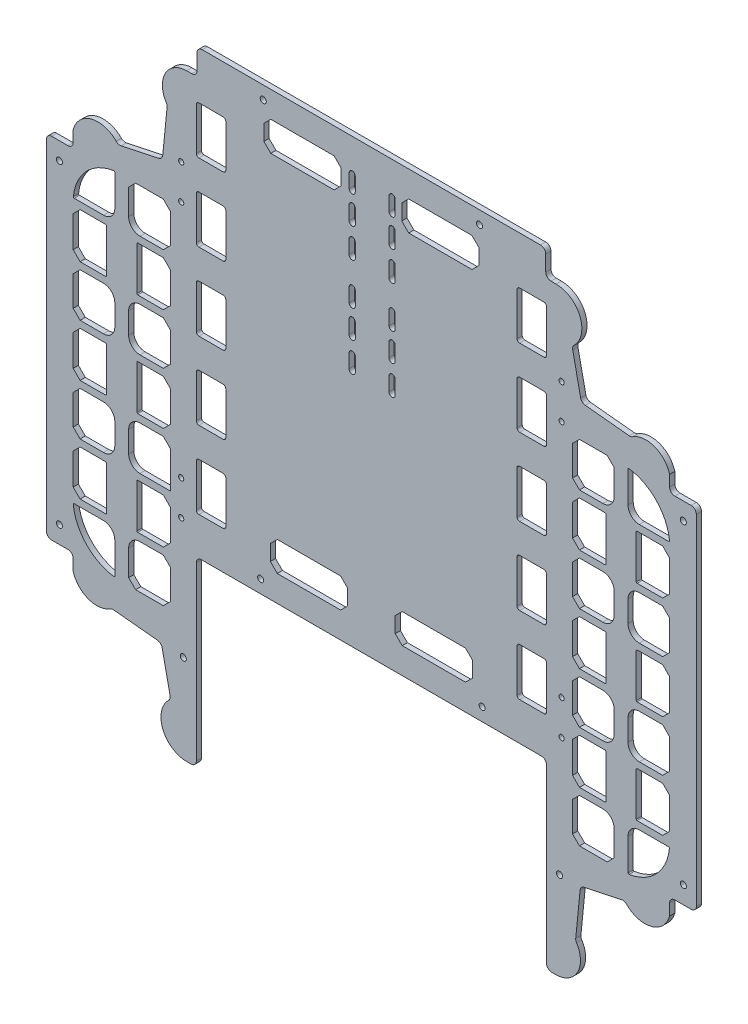
SolidWorks part; units mm, degrees
other "Marcação1"
sketch "Esboço3" plane through (306.3428, -817.7411, 6) normal (0.4912, -0.5914, 0.6395) x (0.7548, 0.6554, 0.0264)
material "Liga 1060"
ref_plane "Plano frontal" through (0, 0, 0) normal (0, 0, 1) x (1, 0, 0)
ref_plane "Plano superior" through (0, 0, 0) normal (0, 1, 0) x (1, 0, 0)
ref_plane "Plano direito" through (0, 0, 0) normal (1, 0, 0) x (0, 0, -1)
sketch "Esboço1" plane through (0, 0, 0) normal (0, 0, 1) x (1, 0, 0)
  line L0 (306.3428, -674.4933) -> (275.5206, -674.4933)
  line L5 (275.5206, -674.4933) -> (275.5206, -717.7786)
  line L6 (175.5581, -775.7411) -> (175.5581, -817.7411)
  line L7 (175.5581, -817.7411) -> (133.5581, -817.7411)
  line L8 (133.5581, -817.7411) -> (133.5581, -607.7411)
  line L9 (233.5206, -717.7786) -> (275.5206, -717.7786)
  line L10 (291.5428, -270.1036) -> (291.5428, -675.5786) construction
  line L12 (291.5428, -472.8411) -> (-428.2572, -472.8411) construction
  line L14 (-428.2572, -675.5786) -> (-428.2572, -472.8411) construction
  line L16 (233.5206, -227.9036) -> (275.5206, -227.9036)
  line L18 (175.5581, -127.9411) -> (133.5581, -127.9411)
  line L19 (175.5581, -169.9411) -> (175.5581, -127.9411)
  line L20 (275.5206, -271.189) -> (275.5206, -227.9036)
  line L21 (306.3428, -271.189) -> (275.5206, -271.189)
  line L23 (132.6775, -97.9411) -> (132.6775, -127.9411)
  line L24 (132.6775, -127.9411) -> (133.5581, -127.9411)
  line L26 (-68.3572, -472.8411) -> (-68.3572, -97.9411) construction
  line L27 (-428.2572, -270.1036) -> (-428.2572, -675.5786) construction
  line L28 (-269.3919, -127.9411) -> (-270.2725, -127.9411)
  line L29 (-269.3919, -97.9411) -> (-269.3919, -127.9411)
  line L30 (-443.0572, -271.189) -> (-412.235, -271.189)
  line L31 (-412.235, -271.189) -> (-412.235, -227.9036)
  line L32 (-312.2725, -169.9411) -> (-312.2725, -127.9411)
  line L33 (-312.2725, -127.9411) -> (-270.2725, -127.9411)
  line L34 (-370.235, -227.9036) -> (-412.235, -227.9036)
  line L35 (-370.235, -717.7786) -> (-412.235, -717.7786)
  line L36 (-270.2725, -817.7411) -> (-270.2725, -607.7411)
  line L37 (-312.2725, -817.7411) -> (-270.2725, -817.7411)
  line L38 (-312.2725, -775.7411) -> (-312.2725, -817.7411)
  line L39 (-412.235, -674.4933) -> (-412.235, -717.7786)
  line L40 (-443.0572, -674.4933) -> (-412.235, -674.4933)
  line L41 (-269.3919, -97.9411) -> (132.6775, -97.9411)
  line L42 (306.3428, -271.189) -> (306.3428, -674.4933)
  line L43 (-443.0572, -271.189) -> (-443.0572, -674.4933)
  line L44 (-270.2725, -607.7411) -> (133.5581, -607.7411)
  arc A0 (233.5206, -717.7786) -> (175.5581, -775.7411) centre (233.5206, -775.7411) ccw
  arc A1 (233.5206, -227.9036) -> (175.5581, -169.9411) centre (233.5206, -169.9411) cw
  arc A2 (-370.235, -227.9036) -> (-312.2725, -169.9411) centre (-370.235, -169.9411) ccw
  arc A3 (-370.235, -717.7786) -> (-312.2725, -775.7411) centre (-370.235, -775.7411) cw
  dimension "D1" = 42
  dimension "D2" = 210
  dimension "D4" = 42
extrude "Ressalto-extrusão1" add sketch "Esboço1" along normal blind 6
fillet "Filete1" radius 6 23 edges at (-443.0572, -271.189, 3) (-412.235, -271.189, 3) (-412.235, -227.9036, 3) (-312.2725, -127.9411, 3) (-269.3919, -127.9411, 3) (-269.3919, -97.9411, 3) (132.6775, -97.9411, 3) (175.5581, -127.9411, 3) (275.5206, -227.9036, 3) (275.5206, -271.189, 3) (306.3428, -271.189, 3) (306.3428, -674.4933, 3) (275.5206, -674.4933, 3) (275.5206, -717.7786, 3) (175.5581, -817.7411, 3) (133.5581, -817.7411, 3) (133.5581, -607.7411, 3) (-270.2725, -607.7411, 3) (-270.2725, -817.7411, 3) (-312.2725, -817.7411, 3) (-412.235, -717.7786, 3) (-412.235, -674.4933, 3) (-443.0572, -674.4933, 3)
sketch "Esboço2" plane through (0, 0, 0) normal (0, 0, -1) x (-1, 0, 0)
  line L0 (309.4474, -230.6211) -> (360.4221, -241.4208)
  line L1 (360.4221, -241.4208) -> (309.4474, -230.6211)
  line L2 (309.4474, -230.6211) -> (303.7025, -173.3327)
  line L3 (68.3572, -97.9411) -> (68.3572, -607.7411) construction
  line L4 (-126.6775, -97.9411) -> (263.3919, -97.9411) construction
  line L5 (264.2725, -607.7411) -> (-127.5581, -607.7411) construction
  line L6 (443.0572, -472.8411) -> (-306.3428, -472.8411) construction
  line L7 (443.0572, -277.189) -> (443.0572, -668.4933) construction
  line L8 (-306.3428, -668.4933) -> (-306.3428, -277.189) construction
  line L9 (310.5772, -713.9314) -> (299.7775, -764.906)
  line L10 (299.7775, -764.906) -> (310.5772, -713.9314)
  line L11 (310.5772, -713.9314) -> (367.8657, -708.1865)
  line L12 (-172.7331, -715.0612) -> (-223.7077, -704.2615)
  line L13 (-223.7077, -704.2615) -> (-172.7331, -715.0612)
  line L14 (-172.7331, -715.0612) -> (-166.9881, -772.3496)
  line L15 (-173.8629, -231.7509) -> (-163.0631, -180.7763)
  line L16 (-163.0631, -180.7763) -> (-173.8629, -231.7509)
  line L17 (-173.8629, -231.7509) -> (-231.1513, -237.4958)
  line L18 (-169.5581, -127.9411) -> (-132.6775, -127.9411) construction
  arc A0 (413.2572, -259.7582) -> (360.4221, -241.4208) centre (383.6575, -259.7582) ccw
  arc A1 (303.7025, -173.3327) -> (281.4232, -127.9623) centre (281.1035, -156.2746) ccw
  arc A2 (413.2572, -259.7582) -> (281.4232, -127.9623) centre (306.4642, -234.748) ccw
  arc A3 (281.4402, -817.7411) -> (299.7775, -764.906) centre (281.4402, -788.1414) ccw
  arc A4 (367.8657, -708.1865) -> (413.2361, -685.9071) centre (384.9237, -685.5874) ccw
  arc A5 (281.4402, -817.7411) -> (413.2361, -685.9071) centre (306.4503, -710.9481) ccw
  arc A6 (-276.5428, -685.9241) -> (-223.7077, -704.2615) centre (-246.9431, -685.9241) ccw
  arc A7 (-166.9881, -772.3496) -> (-144.7088, -817.72) centre (-144.3891, -789.4076) ccw
  arc A8 (-276.5428, -685.9241) -> (-144.7088, -817.72) centre (-169.7498, -710.9343) ccw
  arc A9 (-144.7258, -127.9411) -> (-163.0631, -180.7763) centre (-144.7258, -157.5409) ccw
  arc A10 (-231.1513, -237.4958) -> (-276.5217, -259.7752) centre (-248.2093, -260.0949) ccw
  arc A11 (-144.7258, -127.9411) -> (-276.5217, -259.7752) centre (-169.7359, -234.7341) ccw
  point P20 (68.3572, -472.8411)
  point P48 (68.3572, -472.8411)
  dimension "D1" = 4
extrude "Corte-extrusão1" cut sketch "Esboço2" against normal blind 10
fillet "Filete2" radius 6 13 edges at (-360.4221, -241.4208, 3) (-309.4474, -230.6211, 3) (132.6775, -127.9411, 3) (-367.8657, -708.1865, 3) (-310.5772, -713.9314, 3) (-299.7775, -764.906, 3) (166.9881, -772.3496, 3) (172.7331, -715.0612, 3) (223.7077, -704.2615, 3) (231.1513, -237.4958, 3) (173.8629, -231.7509, 3) (163.0631, -180.7763, 3) (-303.7025, -173.3327, 3)
sketch "Esboço4" plane through (0, 0, 0) normal (0, 0, -1) x (-1, 0, 0)
  line L0 (356.2548, -675.5786) -> (356.2548, -625.0786) construction
  line L1 (373.7548, -625.0786) -> (364.2548, -625.0786)
  line L2 (373.7548, -617.0786) -> (373.7548, -565.0786)
  line L3 (373.7548, -557.0786) -> (364.2548, -557.0786)
  line L4 (338.7548, -617.0786) -> (338.7548, -565.0786)
  line L5 (373.7548, -506.5786) -> (364.2548, -506.5786)
  line L6 (373.7548, -498.5786) -> (373.7548, -446.5786)
  line L7 (373.7548, -438.5786) -> (364.2548, -438.5786)
  line L8 (338.7548, -498.5786) -> (338.7548, -446.5786)
  line L9 (373.7548, -388.0786) -> (364.2548, -388.0786)
  line L10 (373.7548, -380.0786) -> (373.7548, -328.0786)
  line L11 (373.7548, -320.0786) -> (364.2548, -320.0786)
  line L12 (338.7548, -380.0786) -> (338.7548, -328.0786)
  line L13 (356.2548, -557.0786) -> (356.2548, -506.5786) construction
  line L14 (356.2548, -438.5786) -> (356.2548, -388.0786) construction
  line L15 (356.2548, -320.0786) -> (356.2548, -269.5786) construction
  line L16 (68.3572, -607.7411) -> (68.3572, -97.9411) construction
  line L17 (264.2725, -607.7411) -> (-127.5581, -607.7411) construction
  line L18 (-126.6775, -97.9411) -> (263.3919, -97.9411) construction
  line L19 (364.2548, -438.5786) -> (364.2548, -388.0786)
  line L20 (300.2725, -269.5786) -> (348.2548, -269.5786)
  line L21 (300.2725, -269.5786) -> (300.2725, -320.0786)
  line L22 (300.2725, -675.5786) -> (348.2548, -675.5786)
  line L23 (412.2372, -269.5786) -> (412.2372, -320.0786)
  line L24 (364.2548, -320.0786) -> (364.2548, -269.5786)
  line L25 (364.2548, -557.0786) -> (364.2548, -506.5786)
  line L26 (364.2548, -675.5786) -> (364.2548, -625.0786)
  line L27 (348.2548, -438.5786) -> (348.2548, -388.0786)
  line L28 (348.2548, -320.0786) -> (348.2548, -269.5786)
  line L29 (348.2548, -557.0786) -> (348.2548, -506.5786)
  line L30 (348.2548, -675.5786) -> (348.2548, -625.0786)
  line L31 (348.2548, -321.2786) -> (348.2548, -270.7786) construction
  line L32 (364.2548, -321.2786) -> (364.2548, -270.7786) construction
  line L33 (356.2548, -321.2786) -> (356.2548, -270.7786) construction
  line L34 (348.2548, -676.1036) -> (348.2548, -625.0786) construction
  line L35 (364.2548, -676.1036) -> (364.2548, -625.0786) construction
  line L36 (356.2548, -676.1036) -> (356.2548, -625.0786) construction
  line L37 (348.2548, -320.0786) -> (338.7548, -320.0786)
  line L38 (348.2548, -388.0786) -> (338.7548, -388.0786)
  line L39 (348.2548, -438.5786) -> (338.7548, -438.5786)
  line L40 (348.2548, -506.5786) -> (338.7548, -506.5786)
  line L41 (348.2548, -557.0786) -> (338.7548, -557.0786)
  line L42 (348.2548, -625.0786) -> (338.7548, -625.0786)
  line L43 (338.7548, -320.0786) -> (300.2725, -320.0786)
  line L44 (373.7548, -320.0786) -> (412.2372, -320.0786)
  line L45 (338.7548, -388.0786) -> (300.2725, -388.0786)
  line L46 (373.7548, -388.0786) -> (412.2372, -388.0786)
  line L47 (338.7548, -438.5786) -> (300.2725, -438.5786)
  line L48 (373.7548, -438.5786) -> (412.2372, -438.5786)
  line L49 (338.7548, -506.5786) -> (300.2725, -506.5786)
  line L50 (373.7548, -506.5786) -> (412.2372, -506.5786)
  line L51 (373.7548, -557.0786) -> (412.2372, -557.0786)
  line L52 (338.7548, -557.0786) -> (300.2725, -557.0786)
  line L53 (373.7548, -625.0786) -> (412.2372, -625.0786)
  line L54 (338.7548, -625.0786) -> (300.2725, -625.0786)
  line L55 (364.2548, -269.5786) -> (412.2372, -269.5786)
  line L56 (338.7548, -617.0786) -> (300.2725, -617.0786)
  line L57 (300.2725, -328.0786) -> (300.2725, -380.0786)
  line L58 (373.7548, -565.0786) -> (412.2372, -565.0786)
  line L59 (412.2372, -328.0786) -> (412.2372, -380.0786)
  line L60 (338.7548, -498.5786) -> (300.2725, -498.5786)
  line L61 (300.2725, -388.0786) -> (300.2725, -438.5786)
  line L62 (373.7548, -446.5786) -> (412.2372, -446.5786)
  line L63 (412.2372, -388.0786) -> (412.2372, -438.5786)
  line L64 (338.7548, -380.0786) -> (300.2725, -380.0786)
  line L65 (300.2725, -446.5786) -> (300.2725, -498.5786)
  line L66 (373.7548, -328.0786) -> (412.2372, -328.0786)
  line L67 (373.7548, -617.0786) -> (412.2372, -617.0786)
  line L68 (412.2372, -446.5786) -> (412.2372, -498.5786)
  line L69 (338.7548, -565.0786) -> (300.2725, -565.0786)
  line L70 (300.2725, -506.5786) -> (300.2725, -557.0786)
  line L71 (373.7548, -498.5786) -> (412.2372, -498.5786)
  line L72 (412.2372, -506.5786) -> (412.2372, -557.0786)
  line L73 (338.7548, -446.5786) -> (300.2725, -446.5786)
  line L74 (412.2372, -565.0786) -> (412.2372, -617.0786)
  line L75 (373.7548, -380.0786) -> (412.2372, -380.0786)
  line L76 (300.2725, -565.0786) -> (300.2725, -617.0786)
  line L77 (338.7548, -328.0786) -> (300.2725, -328.0786)
  line L78 (300.2725, -625.0786) -> (300.2725, -675.5786)
  line L79 (412.2372, -625.0786) -> (412.2372, -675.5786)
  line L80 (364.2548, -675.5786) -> (412.2372, -675.5786)
  line L81 (-219.5404, -320.0786) -> (-219.5404, -269.5786) construction
  line L82 (-219.5404, -438.5786) -> (-219.5404, -388.0786) construction
  line L83 (-219.5404, -557.0786) -> (-219.5404, -506.5786) construction
  line L84 (-219.5404, -675.5786) -> (-219.5404, -625.0786) construction
  line L85 (-227.5404, -675.5786) -> (-275.5228, -675.5786)
  line L86 (-275.5228, -625.0786) -> (-275.5228, -675.5786)
  line L87 (-163.5581, -625.0786) -> (-163.5581, -675.5786)
  line L88 (-202.0404, -328.0786) -> (-163.5581, -328.0786)
  line L89 (-163.5581, -565.0786) -> (-163.5581, -617.0786)
  line L90 (-237.0404, -380.0786) -> (-275.5228, -380.0786)
  line L91 (-275.5228, -565.0786) -> (-275.5228, -617.0786)
  line L92 (-202.0404, -446.5786) -> (-163.5581, -446.5786)
  line L93 (-275.5228, -506.5786) -> (-275.5228, -557.0786)
  line L94 (-237.0404, -498.5786) -> (-275.5228, -498.5786)
  line L95 (-163.5581, -506.5786) -> (-163.5581, -557.0786)
  line L96 (-202.0404, -565.0786) -> (-163.5581, -565.0786)
  line L97 (-275.5228, -446.5786) -> (-275.5228, -498.5786)
  line L98 (-237.0404, -617.0786) -> (-275.5228, -617.0786)
  line L99 (-237.0404, -328.0786) -> (-275.5228, -328.0786)
  line L100 (-163.5581, -446.5786) -> (-163.5581, -498.5786)
  line L101 (-202.0404, -380.0786) -> (-163.5581, -380.0786)
  line L102 (-275.5228, -388.0786) -> (-275.5228, -438.5786)
  line L103 (-237.0404, -446.5786) -> (-275.5228, -446.5786)
  line L104 (-163.5581, -388.0786) -> (-163.5581, -438.5786)
  line L105 (-202.0404, -498.5786) -> (-163.5581, -498.5786)
  line L106 (-275.5228, -328.0786) -> (-275.5228, -380.0786)
  line L107 (-237.0404, -565.0786) -> (-275.5228, -565.0786)
  line L112 (-163.5581, -328.0786) -> (-163.5581, -380.0786)
  line L113 (-202.0404, -617.0786) -> (-163.5581, -617.0786)
  line L114 (-227.5404, -269.5786) -> (-275.5228, -269.5786)
  line L115 (-202.0404, -625.0786) -> (-163.5581, -625.0786)
  line L116 (-237.0404, -625.0786) -> (-275.5228, -625.0786)
  line L117 (-202.0404, -557.0786) -> (-163.5581, -557.0786)
  line L118 (-237.0404, -557.0786) -> (-275.5228, -557.0786)
  line L119 (-237.0404, -506.5786) -> (-275.5228, -506.5786)
  line L120 (-202.0404, -506.5786) -> (-163.5581, -506.5786)
  line L121 (-237.0404, -438.5786) -> (-275.5228, -438.5786)
  line L122 (-202.0404, -438.5786) -> (-163.5581, -438.5786)
  line L123 (-237.0404, -388.0786) -> (-275.5228, -388.0786)
  line L124 (-202.0404, -388.0786) -> (-163.5581, -388.0786)
  line L125 (-237.0404, -320.0786) -> (-275.5228, -320.0786)
  line L126 (-202.0404, -320.0786) -> (-163.5581, -320.0786)
  line L127 (-211.5404, -625.0786) -> (-202.0404, -625.0786)
  line L128 (-211.5404, -557.0786) -> (-202.0404, -557.0786)
  line L129 (-211.5404, -506.5786) -> (-202.0404, -506.5786)
  line L130 (-211.5404, -438.5786) -> (-202.0404, -438.5786)
  line L131 (-211.5404, -388.0786) -> (-202.0404, -388.0786)
  line L132 (-211.5404, -320.0786) -> (-202.0404, -320.0786)
  line L133 (-211.5404, -675.5786) -> (-211.5404, -625.0786)
  line L134 (-211.5404, -557.0786) -> (-211.5404, -506.5786)
  line L135 (-211.5404, -320.0786) -> (-211.5404, -269.5786)
  line L136 (-211.5404, -438.5786) -> (-211.5404, -388.0786)
  line L137 (-227.5404, -675.5786) -> (-227.5404, -625.0786)
  line L138 (-227.5404, -557.0786) -> (-227.5404, -506.5786)
  line L139 (-227.5404, -320.0786) -> (-227.5404, -269.5786)
  line L140 (-275.5228, -269.5786) -> (-275.5228, -320.0786)
  line L141 (-163.5581, -675.5786) -> (-211.5404, -675.5786)
  line L142 (-163.5581, -269.5786) -> (-163.5581, -320.0786)
  line L143 (-163.5581, -269.5786) -> (-211.5404, -269.5786)
  line L144 (-227.5404, -438.5786) -> (-227.5404, -388.0786)
  line L145 (-202.0404, -380.0786) -> (-202.0404, -328.0786)
  line L146 (-237.0404, -320.0786) -> (-227.5404, -320.0786)
  line L147 (-237.0404, -380.0786) -> (-237.0404, -328.0786)
  line L148 (-237.0404, -388.0786) -> (-227.5404, -388.0786)
  line L149 (-202.0404, -498.5786) -> (-202.0404, -446.5786)
  line L150 (-237.0404, -438.5786) -> (-227.5404, -438.5786)
  line L151 (-237.0404, -498.5786) -> (-237.0404, -446.5786)
  line L152 (-237.0404, -506.5786) -> (-227.5404, -506.5786)
  line L153 (-202.0404, -617.0786) -> (-202.0404, -565.0786)
  line L154 (-237.0404, -557.0786) -> (-227.5404, -557.0786)
  line L155 (-237.0404, -617.0786) -> (-237.0404, -565.0786)
  line L156 (-237.0404, -625.0786) -> (-227.5404, -625.0786)
  dimension "D1" = 68
  dimension "D2" = 35
  dimension "D3" = 406
  dimension "D4" = 8
  dimension "D5" = 8
  dimension "D6" = 8
  dimension "D7" = 8
extrude "Corte-extrusão2" cut sketch "Esboço4" against normal through all
fillet "Filete3" radius 55 4 edges at (-412.2372, -675.5786, 3) (-412.2372, -269.5786, 3) (275.5228, -269.5786, 3) (275.5228, -675.5786, 3)
fillet "Filete4" radius 13 24 edges at (-364.2548, -506.5786, 3) (-364.2548, -388.0786, 3) (-348.2548, -388.0786, 3) (-348.2548, -506.5786, 3) (-348.2548, -438.5786, 3) (-348.2548, -320.0786, 3) (-364.2548, -320.0786, 3) (-364.2548, -438.5786, 3) (-364.2548, -557.0786, 3) (-348.2548, -557.0786, 3) (-364.2548, -625.0786, 3) (-348.2548, -625.0786, 3) (211.5404, -320.0786, 3) (211.5404, -438.5786, 3) (211.5404, -557.0786, 3) (227.5404, -557.0786, 3) (227.5404, -438.5786, 3) (227.5404, -320.0786, 3) (227.5404, -388.0786, 3) (227.5404, -506.5786, 3) (227.5404, -625.0786, 3) (211.5404, -625.0786, 3) (211.5404, -506.5786, 3) (211.5404, -388.0786, 3)
chamfer "Chanfro1" distance 8 angle 45 51 edges at (-348.2548, -675.5786, 3) (-348.2548, -269.5786, 3) (-412.2372, -328.0786, 3) (-412.2372, -388.0786, 3) (-412.2372, -446.5786, 3) (-412.2372, -506.5786, 3) (-412.2372, -565.0786, 3) (-412.2372, -617.0786, 3) (-412.2372, -557.0786, 3) (-412.2372, -498.5786, 3) (-412.2372, -438.5786, 3) (-412.2372, -380.0786, 3) (-300.2725, -320.0786, 3) (-300.2725, -380.0786, 3) (-300.2725, -438.5786, 3) (-300.2725, -498.5786, 3) (-300.2725, -617.0786, 3) (-300.2725, -675.5786, 3) (-300.2725, -269.5786, 3) (-300.2725, -328.0786, 3) (-300.2725, -388.0786, 3) (-300.2725, -446.5786, 3) (-300.2725, -506.5786, 3) (-300.2725, -565.0786, 3) (-300.2725, -625.0786, 3) (211.5404, -675.5786, 3) (275.5228, -617.0786, 3) (275.5228, -557.0786, 3) (275.5228, -498.5786, 3) (275.5228, -438.5786, 3) (275.5228, -380.0786, 3) (275.5228, -565.0786, 3) (275.5228, -506.5786, 3) (275.5228, -446.5786, 3) (275.5228, -388.0786, 3) (275.5228, -328.0786, 3) (211.5404, -269.5786, 3) (163.5581, -625.0786, 3) (163.5581, -565.0786, 3) (163.5581, -506.5786, 3) (163.5581, -446.5786, 3) (163.5581, -388.0786, 3) (163.5581, -328.0786, 3) (163.5581, -269.5786, 3) (163.5581, -320.0786, 3) (163.5581, -380.0786, 3) (163.5581, -438.5786, 3) (163.5581, -498.5786, 3) (163.5581, -557.0786, 3) (163.5581, -617.0786, 3) (163.5581, -675.5786, 3)
fillet "Filete5" radius 1 32 edges at (-364.2548, -675.1525, 3) (-412.2372, -625.0786, 3) (-364.2548, -269.5786, 3) (-412.0878, -320.0786, 3) (-338.7548, -617.0786, 3) (-338.7548, -498.5786, 3) (-338.7548, -380.0786, 3) (-373.7548, -617.0786, 3) (-373.7548, -498.5786, 3) (-373.7548, -380.0786, 3) (-373.7548, -328.0786, 3) (-373.7548, -446.5786, 3) (-373.7548, -565.0786, 3) (-338.7548, -565.0786, 3) (-338.7548, -328.0786, 3) (-338.7548, -446.5786, 3) (237.0404, -565.0786, 3) (237.0404, -446.5786, 3) (227.5404, -270.0048, 3) (237.0404, -328.0786, 3) (202.0404, -328.0786, 3) (202.0404, -446.5786, 3) (202.0404, -565.0786, 3) (275.3734, -625.0786, 3) (227.5404, -675.5786, 3) (237.0404, -617.0786, 3) (237.0404, -498.5786, 3) (237.0404, -380.0786, 3) (275.5228, -320.0786, 3) (202.0404, -380.0786, 3) (202.0404, -498.5786, 3) (202.0404, -617.0786, 3)
sketch "Esboço8" plane through (0, 0, 0) normal (0, 0, -1) x (-1, 0, 0)
  line L0 (270.2725, -508.9411) -> (270.2725, -474.9411) construction
  line L1 (270.2725, -563.9411) -> (236.2725, -563.9411)
  line L2 (270.2725, -563.9411) -> (270.2725, -508.9411)
  line L3 (270.2725, -508.9411) -> (236.2725, -508.9411)
  line L4 (236.2725, -563.9411) -> (236.2725, -508.9411)
  line L9 (270.2725, -152.9411) -> (236.2725, -152.9411)
  line L10 (270.2725, -152.9411) -> (270.2725, -207.9411)
  line L11 (270.2725, -207.9411) -> (236.2725, -207.9411)
  line L12 (236.2725, -152.9411) -> (236.2725, -207.9411)
  line L17 (270.2725, -474.9411) -> (236.2725, -474.9411)
  line L18 (270.2725, -474.9411) -> (270.2725, -419.9411)
  line L19 (270.2725, -419.9411) -> (236.2725, -419.9411)
  line L20 (236.2725, -474.9411) -> (236.2725, -419.9411)
  line L21 (270.2725, -385.9411) -> (236.2725, -385.9411)
  line L22 (270.2725, -385.9411) -> (270.2725, -330.9411)
  line L23 (270.2725, -330.9411) -> (236.2725, -330.9411)
  line L24 (236.2725, -385.9411) -> (236.2725, -330.9411)
  line L25 (270.2725, -296.9411) -> (236.2725, -296.9411)
  line L26 (270.2725, -296.9411) -> (270.2725, -241.9411)
  line L27 (270.2725, -241.9411) -> (236.2725, -241.9411)
  line L28 (236.2725, -296.9411) -> (236.2725, -241.9411)
  line L53 (270.2725, -419.9411) -> (270.2725, -385.9411) construction
  line L54 (270.2725, -207.9411) -> (270.2725, -241.9411) construction
  line L55 (270.2725, -296.9411) -> (270.2725, -330.9411) construction
  line L56 (-133.5581, -296.9411) -> (-133.5581, -330.9411) construction
  line L57 (-133.5581, -207.9411) -> (-133.5581, -241.9411) construction
  line L58 (-133.5581, -419.9411) -> (-133.5581, -385.9411) construction
  line L59 (300.2725, -277.5786) -> (300.2725, -312.0786) construction
  line L60 (-126.6775, -97.9411) -> (263.3919, -97.9411) construction
  line L61 (-133.5581, -508.9411) -> (-133.5581, -474.9411) construction
  line L62 (68.3572, -97.9411) -> (68.3572, -607.7411) construction
  line L63 (264.2725, -607.7411) -> (-127.5581, -607.7411) construction
  line L64 (-99.5581, -296.9411) -> (-99.5581, -241.9411)
  line L65 (-133.5581, -241.9411) -> (-99.5581, -241.9411)
  line L66 (-133.5581, -296.9411) -> (-133.5581, -241.9411)
  line L67 (-133.5581, -296.9411) -> (-99.5581, -296.9411)
  line L68 (-99.5581, -385.9411) -> (-99.5581, -330.9411)
  line L69 (-133.5581, -330.9411) -> (-99.5581, -330.9411)
  line L70 (-133.5581, -385.9411) -> (-133.5581, -330.9411)
  line L71 (-133.5581, -385.9411) -> (-99.5581, -385.9411)
  line L72 (-99.5581, -474.9411) -> (-99.5581, -419.9411)
  line L73 (-133.5581, -419.9411) -> (-99.5581, -419.9411)
  line L74 (-133.5581, -474.9411) -> (-133.5581, -419.9411)
  line L75 (-133.5581, -474.9411) -> (-99.5581, -474.9411)
  line L76 (-99.5581, -152.9411) -> (-99.5581, -207.9411)
  line L77 (-133.5581, -207.9411) -> (-99.5581, -207.9411)
  line L78 (-133.5581, -152.9411) -> (-133.5581, -207.9411)
  line L79 (-133.5581, -152.9411) -> (-99.5581, -152.9411)
  line L80 (-99.5581, -563.9411) -> (-99.5581, -508.9411)
  line L81 (-133.5581, -508.9411) -> (-99.5581, -508.9411)
  line L82 (-133.5581, -563.9411) -> (-133.5581, -508.9411)
  line L83 (-133.5581, -563.9411) -> (-99.5581, -563.9411)
  dimension "D1" = 30
  dimension "D2" = 55
  dimension "D3" = 34
  dimension "D4" = 55
  dimension "D5" = 34
extrude "Corte-extrusão4" cut sketch "Esboço8" against normal through all
fillet "Filete6" radius 3 40 edges at (99.5581, -563.9411, 3) (99.5581, -474.9411, 3) (99.5581, -385.9411, 3) (99.5581, -296.9411, 3) (99.5581, -207.9411, 3) (-270.2725, -207.9411, 3) (-270.2725, -296.9411, 3) (-270.2725, -385.9411, 3) (-270.2725, -474.9411, 3) (-270.2725, -563.9411, 3) (-236.2725, -508.9411, 3) (-236.2725, -419.9411, 3) (-236.2725, -330.9411, 3) (-236.2725, -241.9411, 3) (-236.2725, -152.9411, 3) (-236.2725, -207.9411, 3) (-236.2725, -296.9411, 3) (-236.2725, -385.9411, 3) (-236.2725, -474.9411, 3) (-236.2725, -563.9411, 3) (133.5581, -563.9411, 3) (133.5581, -474.9411, 3) (133.5581, -385.9411, 3) (133.5581, -296.9411, 3) (133.5581, -207.9411, 3) (-270.2725, -508.9411, 3) (-270.2725, -419.9411, 3) (-270.2725, -330.9411, 3) (-270.2725, -241.9411, 3) (-270.2725, -152.9411, 3) (99.5581, -508.9411, 3) (99.5581, -419.9411, 3) (99.5581, -330.9411, 3) (99.5581, -241.9411, 3) (133.5581, -508.9411, 3) (133.5581, -419.9411, 3) (133.5581, -330.9411, 3) (133.5581, -241.9411, 3) (99.5581, -152.9411, 3) (133.5581, -152.9411, 3)
sketch "Esboço9" plane through (0, 0, 6) normal (0, 0, 1) x (1, 0, 0)
  line L0 (126.6775, -97.9411) -> (-263.3919, -97.9411) construction
  line L1 (-192.3572, -127.9411) -> (-103.3572, -127.9411)
  line L2 (-192.3572, -127.9411) -> (-192.3572, -161.9411)
  line L3 (-192.3572, -161.9411) -> (-103.3572, -161.9411)
  line L4 (-103.3572, -127.9411) -> (-103.3572, -161.9411)
  line L5 (-33.3572, -127.9411) -> (55.6428, -127.9411)
  line L6 (-33.3572, -127.9411) -> (-33.3572, -161.9411)
  line L7 (-33.3572, -161.9411) -> (55.6428, -161.9411)
  line L8 (55.6428, -127.9411) -> (55.6428, -161.9411)
  line L9 (-236.2725, -180.4411) -> (99.5581, -180.4411) construction
  line L10 (-236.2725, -155.9411) -> (-236.2725, -204.9411) construction
  line L11 (99.5581, -204.9411) -> (99.5581, -155.9411) construction
  line L12 (-103.3572, -161.9411) -> (-33.3572, -161.9411) construction
  line L13 (-68.3572, -161.9411) -> (-68.3572, -180.4411) construction
  line L14 (-264.2725, -607.7411) -> (127.5581, -607.7411) construction
  line L17 (-68.3572, -554.9411) -> (-68.3572, -536.4411) construction
  line L18 (-95.8572, -543.7411) -> (-40.8572, -543.7411) construction
  line L19 (48.1428, -577.7411) -> (48.1428, -543.7411)
  line L20 (-40.8572, -543.7411) -> (48.1428, -543.7411)
  line L21 (-40.8572, -577.7411) -> (-40.8572, -543.7411)
  line L22 (-40.8572, -577.7411) -> (48.1428, -577.7411)
  line L23 (-95.8572, -577.7411) -> (-95.8572, -543.7411)
  line L24 (-184.8572, -543.7411) -> (-95.8572, -543.7411)
  line L25 (-184.8572, -577.7411) -> (-184.8572, -543.7411)
  line L26 (-184.8572, -577.7411) -> (-95.8572, -577.7411)
  dimension "D1" = 30
  dimension "D2" = 30
  dimension "D3" = 89
  dimension "D4" = 89
  dimension "D5" = 70
  dimension "D6" = 34
  dimension "D7" = 30
  dimension "D8" = 30
extrude "Corte-extrusão5" cut sketch "Esboço9" against normal through all
chamfer "Chanfro2" distance 8 angle 45 8 edges at (55.6428, -127.9411, 3) (55.6428, -161.9411, 3) (-33.3572, -127.9411, 3) (-33.3572, -161.9411, 3) (-192.3572, -161.9411, 3) (-192.3572, -127.9411, 3) (-103.3572, -127.9411, 3) (-103.3572, -161.9411, 3)
chamfer "Chanfro3" distance 8 angle 45 8 edges at (48.1428, -543.7411, 3) (-95.8572, -543.7411, 3) (-184.8572, -543.7411, 3) (-40.8572, -543.7411, 3) (-40.8572, -577.7411, 3) (-184.8572, -577.7411, 3) (-95.8572, -577.7411, 3) (48.1428, -577.7411, 3)
sketch "Esboço10" plane through (0, 0, 6) normal (0, 0, 1) x (1, 0, 0)
  line L0 (-44.4725, -135.9411) -> (-44.4725, -151.9411) construction
  line L1 (-40.9725, -135.9411) -> (-40.9725, -151.9411)
  line L2 (-47.9725, -135.9411) -> (-47.9725, -151.9411)
  line L3 (-44.4725, -167.9411) -> (-44.4725, -183.9411) construction
  line L4 (-40.8763, -167.9411) -> (-40.8763, -183.9411)
  line L5 (-48.0686, -167.9411) -> (-48.0686, -183.9411)
  line L6 (-90.4725, -135.9411) -> (-90.4725, -151.9411) construction
  line L9 (-86.9725, -135.9411) -> (-86.9725, -151.9411)
  line L12 (-93.9725, -135.9411) -> (-93.9725, -151.9411)
  line L13 (-90.4725, -167.9411) -> (-90.4725, -183.9411) construction
  line L14 (-86.8763, -167.9411) -> (-86.8763, -183.9411)
  line L15 (-94.0686, -167.9411) -> (-94.0686, -183.9411)
  line L16 (-90.4725, -249.9411) -> (-90.4725, -265.9411) construction
  line L17 (-86.9725, -249.9411) -> (-86.9725, -265.9411)
  line L18 (-93.9725, -249.9411) -> (-93.9725, -265.9411)
  line L19 (-90.4725, -281.9411) -> (-90.4725, -297.9411) construction
  line L20 (-86.8763, -281.9411) -> (-86.8763, -297.9411)
  line L21 (-94.0686, -281.9411) -> (-94.0686, -297.9411)
  line L22 (-44.4725, -249.9411) -> (-44.4725, -265.9411) construction
  line L23 (-40.9725, -249.9411) -> (-40.9725, -265.9411)
  line L24 (-47.9725, -249.9411) -> (-47.9725, -265.9411)
  line L25 (-44.4725, -281.9411) -> (-44.4725, -297.9411) construction
  line L26 (-40.8763, -281.9411) -> (-40.8763, -297.9411)
  line L27 (-48.0686, -281.9411) -> (-48.0686, -297.9411)
  line L28 (-44.4725, -201.9411) -> (-44.4725, -217.9411) construction
  line L29 (-40.8763, -201.9411) -> (-40.8763, -217.9411)
  line L30 (-48.0686, -201.9411) -> (-48.0686, -217.9411)
  line L31 (-90.4725, -201.9411) -> (-90.4725, -217.9411) construction
  line L32 (-86.8763, -201.9411) -> (-86.8763, -217.9411)
  line L33 (-94.0686, -201.9411) -> (-94.0686, -217.9411)
  line L34 (-90.4725, -315.9411) -> (-90.4725, -331.9411) construction
  line L35 (-86.8763, -315.9411) -> (-86.8763, -331.9411)
  line L36 (-94.0686, -315.9411) -> (-94.0686, -331.9411)
  line L37 (-44.4725, -315.9411) -> (-44.4725, -331.9411) construction
  line L38 (-40.8763, -315.9411) -> (-40.8763, -331.9411)
  line L39 (-48.0686, -315.9411) -> (-48.0686, -331.9411)
  arc A0 (-40.9725, -135.9411) -> (-47.9725, -135.9411) centre (-44.4725, -135.9411) ccw
  arc A1 (-47.9725, -151.9411) -> (-40.9725, -151.9411) centre (-44.4725, -151.9411) ccw
  arc A2 (-40.8763, -167.9411) -> (-48.0686, -167.9411) centre (-44.4725, -167.9411) ccw
  arc A3 (-48.0686, -183.9411) -> (-40.8763, -183.9411) centre (-44.4725, -183.9411) ccw
  arc A8 (-86.9725, -135.9411) -> (-93.9725, -135.9411) centre (-90.4725, -135.9411) ccw
  arc A9 (-93.9725, -151.9411) -> (-86.9725, -151.9411) centre (-90.4725, -151.9411) ccw
  arc A10 (-86.8763, -167.9411) -> (-94.0686, -167.9411) centre (-90.4725, -167.9411) ccw
  arc A11 (-94.0686, -183.9411) -> (-86.8763, -183.9411) centre (-90.4725, -183.9411) ccw
  arc A12 (-86.9725, -249.9411) -> (-93.9725, -249.9411) centre (-90.4725, -249.9411) ccw
  arc A13 (-93.9725, -265.9411) -> (-86.9725, -265.9411) centre (-90.4725, -265.9411) ccw
  arc A14 (-86.8763, -281.9411) -> (-94.0686, -281.9411) centre (-90.4725, -281.9411) ccw
  arc A15 (-94.0686, -297.9411) -> (-86.8763, -297.9411) centre (-90.4725, -297.9411) ccw
  arc A16 (-40.9725, -249.9411) -> (-47.9725, -249.9411) centre (-44.4725, -249.9411) ccw
  arc A17 (-47.9725, -265.9411) -> (-40.9725, -265.9411) centre (-44.4725, -265.9411) ccw
  arc A18 (-40.8763, -281.9411) -> (-48.0686, -281.9411) centre (-44.4725, -281.9411) ccw
  arc A19 (-48.0686, -297.9411) -> (-40.8763, -297.9411) centre (-44.4725, -297.9411) ccw
  arc A20 (-40.8763, -201.9411) -> (-48.0686, -201.9411) centre (-44.4725, -201.9411) ccw
  arc A21 (-48.0686, -217.9411) -> (-40.8763, -217.9411) centre (-44.4725, -217.9411) ccw
  arc A22 (-86.8763, -201.9411) -> (-94.0686, -201.9411) centre (-90.4725, -201.9411) ccw
  arc A23 (-94.0686, -217.9411) -> (-86.8763, -217.9411) centre (-90.4725, -217.9411) ccw
  arc A24 (-86.8763, -315.9411) -> (-94.0686, -315.9411) centre (-90.4725, -315.9411) ccw
  arc A25 (-94.0686, -331.9411) -> (-86.8763, -331.9411) centre (-90.4725, -331.9411) ccw
  arc A26 (-40.8763, -315.9411) -> (-48.0686, -315.9411) centre (-44.4725, -315.9411) ccw
  arc A27 (-48.0686, -331.9411) -> (-40.8763, -331.9411) centre (-44.4725, -331.9411) ccw
  point P2 (-44.4725, -143.9411)
  point P7 (-44.4725, -175.9411)
  point P16 (-44.4725, -209.9411)
  point P19 (-90.4725, -143.9411)
  point P24 (-90.4725, -175.9411)
  point P33 (-90.4725, -257.9411)
  point P38 (-90.4725, -289.9411)
  point P47 (-44.4725, -257.9411)
  point P52 (-44.4725, -289.9411)
  point P65 (-90.4725, -209.9411)
  point P72 (-90.4725, -323.9411)
  point P79 (-44.4725, -323.9411)
  dimension "D3" = 3.5
  dimension "D1" = 16
  dimension "D2" = 16
  dimension "D4" = 2
  dimension "D5" = 2
  dimension "D6" = 2
  dimension "D7" = 2
extrude "Corte-extrusão6" cut sketch "Esboço10" against normal through all
sketch "Esboço11" plane through (0, 0, 6) normal (0, 0, 1) x (1, 0, 0)
  line L0 (-68.3572, -97.9411) -> (-68.3572, -607.7411) construction
  line L1 (126.6775, -97.9411) -> (-263.3919, -97.9411) construction
  line L2 (-264.2725, -607.7411) -> (127.5581, -607.7411) construction
  circle A0 centre (150.9805, -222.0786) radius 3
  circle A1 centre (150.9805, -262.0786) radius 3
  circle A2 centre (150.9805, -537.5786) radius 3
  circle A3 centre (150.9805, -577.5786) radius 3
  circle A4 centre (-287.6949, -577.5786) radius 3
  circle A5 centre (-287.6949, -537.5786) radius 3
  circle A6 centre (-287.6949, -262.0786) radius 3
  circle A7 centre (-287.6949, -222.0786) radius 3
extrude "Corte-extrusão7" cut sketch "Esboço11" against normal through all
sketch "Esboço12" plane through (0, 0, 6) normal (0, 0, 1) x (1, 0, 0)
  line L0 (291.3428, -291.189) -> (291.3428, -654.4933) construction
  line L1 (126.6775, -97.9411) -> (-263.3919, -97.9411) construction
  line L2 (306.3428, -668.4933) -> (306.3428, -277.189) construction
  line L3 (300.3428, -271.189) -> (281.5206, -271.189) construction
  line L4 (281.5206, -674.4933) -> (300.3428, -674.4933) construction
  line L5 (-264.2725, -607.7411) -> (127.5581, -607.7411) construction
  line L6 (133.5581, -613.7411) -> (133.5581, -811.7411) construction
  line L7 (-68.3572, -97.9411) -> (-68.3572, -607.7411) construction
  line L8 (-428.0572, -291.189) -> (-428.0572, -654.4933) construction
  circle A0 centre (291.3428, -291.189) radius 3.5
  circle A1 centre (291.3428, -654.4933) radius 3.5
  circle A2 centre (148.5581, -715.7411) radius 3.5
  circle A3 centre (59.3428, -592.7411) radius 3.5
  circle A4 centre (56.3428, -112.9411) radius 3.5
  circle A5 centre (-193.0572, -112.9411) radius 3.5
  circle A6 centre (-196.0572, -592.7411) radius 3.5
  circle A7 centre (-285.2725, -715.7411) radius 3.5
  circle A8 centre (-428.0572, -654.4933) radius 3.5
  circle A9 centre (-428.0572, -291.189) radius 3.5
  dimension "D1" = 7
  dimension "D5" = 20
  dimension "D6" = 20
  dimension "D7" = 232
  dimension "D8" = 15
  dimension "D9" = 108
  dimension "D10" = 15
  dimension "D2" = 15
  dimension "D3" = 250
  dimension "D4" = 15
extrude "Corte-extrusão8" cut sketch "Esboço12" against normal through all
